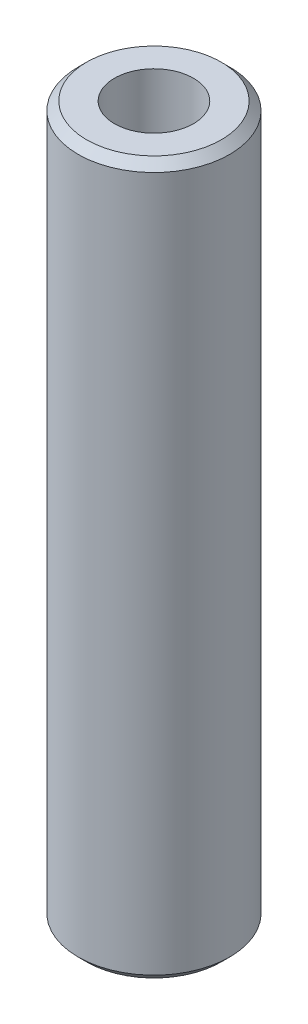
SolidWorks part; units mm, degrees
ref_plane "Front Plane" through (0, 0, 0) normal (0, 0, 1) x (1, 0, 0)
ref_plane "Top Plane" through (0, 0, 0) normal (0, 1, 0) x (1, 0, 0)
ref_plane "Right Plane" through (0, 0, 0) normal (1, 0, 0) x (0, 0, -1)
sketch "Sketch1" plane through (0, 0, 0) normal (0, 1, 0) x (1, 0, 0)
  circle A0 centre (0, 0) radius 42.5
  dimension "SHAFT_OD" = 85
extrude "Boss-Extrude1" add sketch "Sketch1" along normal blind 399.3892
sketch "Sketch2" plane through (0, 0, 0) normal (0, 1, 0) x (1, 0, 0)
  circle A0 centre (0, 0) radius 22.15
  dimension "BORE_D" = 44.3
extrude "Cut-Extrude1" cut sketch "Sketch2" along normal through all
chamfer "Chamfer1" distance 4.7321 angle 45 2 edges at (0, 399.3892, 42.5) (0, 0, 42.5)
